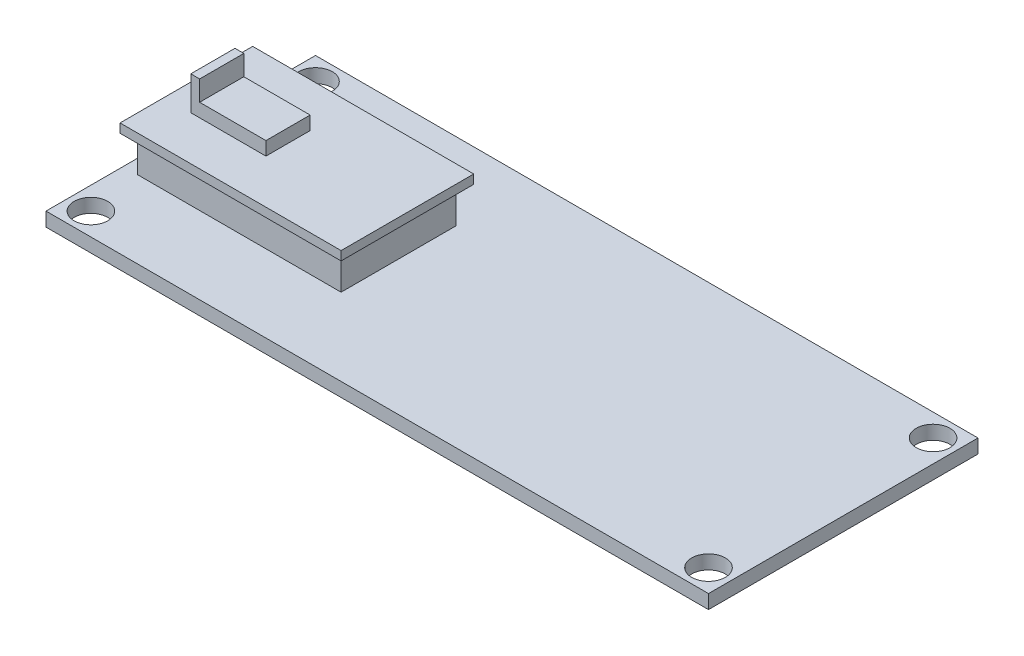
SolidWorks part; units mm, degrees
ref_plane "Front Plane" through (0, 0, 0) normal (0, 0, 1) x (1, 0, 0)
ref_plane "Top Plane" through (0, 0, 0) normal (0, 1, 0) x (1, 0, 0)
ref_plane "Right Plane" through (0, 0, 0) normal (1, 0, 0) x (0, 0, -1)
sketch "Sketch1" plane through (0, 0, 0) normal (0, 1, 0) x (1, 0, 0)
  line L5 (-37.465, -15.24) -> (37.465, -15.24)
  line L6 (-37.465, -15.24) -> (-37.465, 15.24)
  line L7 (-37.465, 15.24) -> (37.465, 15.24)
  line L8 (37.465, -15.24) -> (37.465, 15.24)
  line L9 (-37.465, -15.24) -> (37.465, 15.24) construction
  line L10 (-37.465, 15.24) -> (37.465, -15.24) construction
  line L15 (-34.925, -12.7) -> (34.925, -12.7) construction
  line L16 (-34.925, -12.7) -> (-34.925, 12.7) construction
  line L17 (-34.925, 12.7) -> (34.925, 12.7) construction
  line L18 (34.925, -12.7) -> (34.925, 12.7) construction
  line L19 (-34.925, -12.7) -> (34.925, 12.7) construction
  line L20 (-34.925, 12.7) -> (34.925, -12.7) construction
  circle A0 centre (-34.925, 12.7) radius 1.905
  circle A1 centre (34.925, 12.7) radius 1.905
  circle A2 centre (-34.925, -12.7) radius 1.905
  circle A3 centre (34.925, -12.7) radius 1.905
  point P0 (0, 0)
  point P5 (0, 0)
extrude "Boss-Extrude1" add sketch "Sketch1" against normal blind 1.5748
sketch "Sketch2" plane through (0, 0, 0) normal (0, 1, 0) x (1, 0, 0)
  line L0 (-37.465, 15.24) -> (-37.465, -15.24) construction
  line L1 (37.465, -15.24) -> (37.465, 15.24) construction
  line L2 (-1000, 0) -> (49000, 0) construction
  line L3 (-36.83, 12.7) -> (-36.83, -12.7) construction
  line L4 (-36.83, -7.5) -> (-36.83, 7.5) construction
  line L5 (-36.83, 0) -> (-11.83, 0)
  line L6 (-11.83, -7.5) -> (-11.83, 7.5) construction
  line L8 (-36.83, -7.5) -> (-11.83, -7.5)
  line L9 (-36.83, -7.5) -> (-36.83, 7.5)
  line L10 (-36.83, 7.5) -> (-11.83, 7.5)
  line L11 (-11.83, -7.5) -> (-11.83, 7.5)
  circle A0 centre (-34.925, 12.7) radius 1.905 construction
  circle A1 centre (-34.925, -12.7) radius 1.905 construction
  point P0 (-37.465, 0)
  point P1 (37.465, 0)
  point P7 (-36.83, 12.7)
  point P10 (-36.83, -12.7)
  point P20 (-36.83, 0)
  point P25 (-11.83, 0)
extrude "Boss-Extrude2" add sketch "Sketch2" along normal blind 5.08 contours L5 L11 L10 L9 | L8 L11 L5 L9 region at (-24.33, 0, -3.75) region at (-24.33, 0, 3.75)
sketch "Sketch3" plane through (0, 5.08, 0) normal (0, 1, 0) x (1, 0, 0)
  line L0 (-36.83, -7.5) -> (-11.83, -7.5) construction
  line L1 (-36.83, -7.5) -> (-36.83, 7.5) construction
  line L3 (-35.83, 6.5) -> (-12.83, 6.5)
  line L4 (-35.83, 6.5) -> (-35.83, -6.5)
  line L5 (-35.83, -6.5) -> (-12.83, -6.5)
  line L6 (-12.83, 6.5) -> (-12.83, -6.5)
  line L7 (-36.83, 7.5) -> (-11.83, 7.5)
  line L8 (-36.83, 7.5) -> (-36.83, -7.5)
  line L9 (-36.83, -7.5) -> (-11.83, -7.5)
  line L10 (-11.83, 7.5) -> (-11.83, -7.5)
  point P0 (-36.83, 7.5)
  point P1 (-11.83, -7.5)
  point P3 (-11.83, 7.5)
  point P5 (-36.83, -7.5)
  point P7 (-35.83, -7.5)
  point P9 (-36.83, 6.5)
  point P12 (-36.83, -6.5)
  point P15 (-12.83, -7.5)
  point P16 (-35.83, -6.5)
  point P17 (-12.83, -6.5)
  point P18 (-35.83, 6.5)
  point P19 (-12.83, 6.5)
  dimension "D1" = 1
  dimension "D2" = 1
  dimension "D3" = 1
  dimension "D4" = 1
extrude "Cut-Extrude1" cut sketch "Sketch3" against normal blind 4.064 from offset 1.016 offset against normal yes
sketch "Sketch4" plane through (0, 5.08, 0) normal (0, 1, 0) x (1, 0, 0)
  line L0 (-36.83, -7.5) -> (-11.83, -7.5) construction
  line L1 (-11.83, -7.5) -> (-11.83, 7.5) construction
  line L2 (-36.83, -7.5) -> (-36.83, 7.5) construction
  line L3 (-36.83, -2.5) -> (-36.83, 2.5) construction
  line L5 (-33.83, -2.5) -> (-25.33, -2.5)
  line L6 (-33.83, -2.5) -> (-33.83, 2.5)
  line L7 (-33.83, 2.5) -> (-25.33, 2.5)
  line L8 (-25.33, -2.5) -> (-25.33, 2.5)
  point P0 (-36.83, -7.5)
  point P1 (-33.83, -7.5)
  point P3 (-11.83, -7.5)
  point P6 (-24.33, -7.5)
  point P9 (-25.33, -7.5)
  point P10 (-36.83, 0)
  point P16 (-36.83, 0)
  dimension "D1" = 3
  dimension "D2" = 1
extrude "Boss-Extrude3" add sketch "Sketch4" along normal blind 1.524 contours L6 L5 L8 L7
sketch "Sketch5" plane through (0, 6.604, 0) normal (0, 1, 0) x (1, 0, 0)
  line L0 (-33.83, -2.5) -> (-25.33, -2.5) construction
  line L2 (-32.83, -2.5) -> (-33.83, -2.5)
  line L3 (-32.83, -2.5) -> (-32.83, 2.5)
  line L4 (-32.83, 2.5) -> (-33.83, 2.5)
  line L5 (-33.83, -2.5) -> (-33.83, 2.5)
  point P0 (-33.83, -2.5)
  point P1 (-32.83, -2.5)
  dimension "D1" = 1
extrude "Boss-Extrude4" add sketch "Sketch5" along normal blind 2.286
